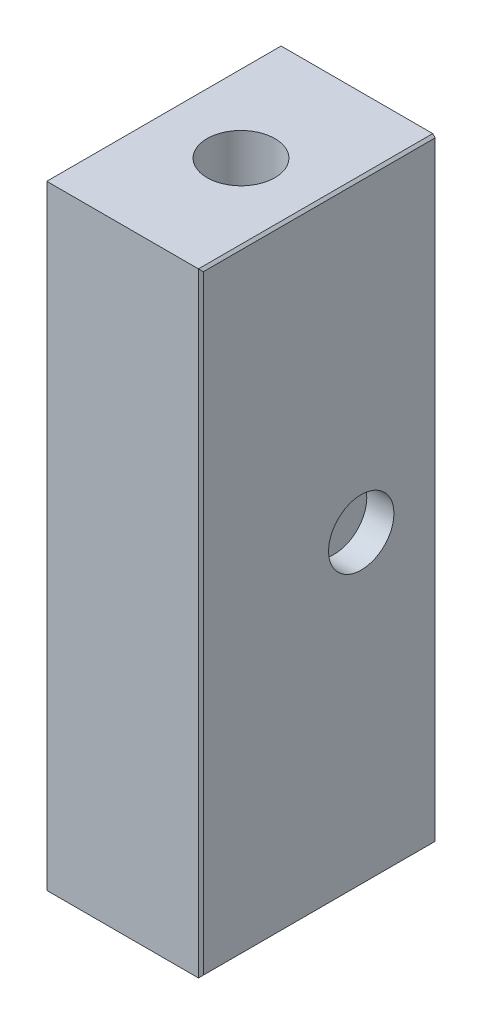
SolidWorks part; units mm, degrees
material "ABS"
ref_plane "Front Plane" through (0, 0, 0) normal (0, 0, 1) x (1, 0, 0)
ref_plane "Top Plane" through (0, 0, 0) normal (0, 1, 0) x (1, 0, 0)
ref_plane "Right Plane" through (0, 0, 0) normal (1, 0, 0) x (0, 0, -1)
sketch "Sketch1" plane through (0, 0, 0) normal (0, 1, 0) x (1, 0, 0)
  line L6 (6.25, -9.5) -> (-6.25, -9.5)
  line L9 (6.25, -9.5) -> (6.25, 9.5)
  line L10 (6.25, 9.5) -> (-6.25, 9.5)
  line L11 (-6.25, -9.5) -> (-6.25, 9.5)
  line L13 (6.25, -9.5) -> (-6.25, 9.5) construction
  line L14 (6.25, 9.5) -> (-6.25, -9.5) construction
  circle A2 centre (0, 0) radius 2.75
  point P0 (0, 0)
  point P9 (0, 0)
  point P10 (0, 0)
  point P11 (0, 0)
  point P12 (0, 0)
  point P13 (0, 0)
  dimension "D2" = 5.5
  dimension "D1" = 12.5
  dimension "D3" = 19
extrude "Boss-Extrude1" add sketch "Sketch1" along normal mid plane 49.8
sketch "Sketch2" plane through (6.25, 0, 0) normal (1, 0, 0) x (0, 0, -1)
  line L3 (-9.5, -25) -> (-9.5, 25) construction
  circle A0 centre (3.5, 0) radius 2.65
  dimension "D1" = 5.3
  dimension "D2" = 13
extrude "Cut-Extrude1" cut sketch "Sketch2" against normal blind 2.2
chamfer "Chamfer1" distance 0.2 angle 45 3 edges at (6.25, -24.9, 0) (6.25, 0, 9.5) (6.25, 24.9, 0)
